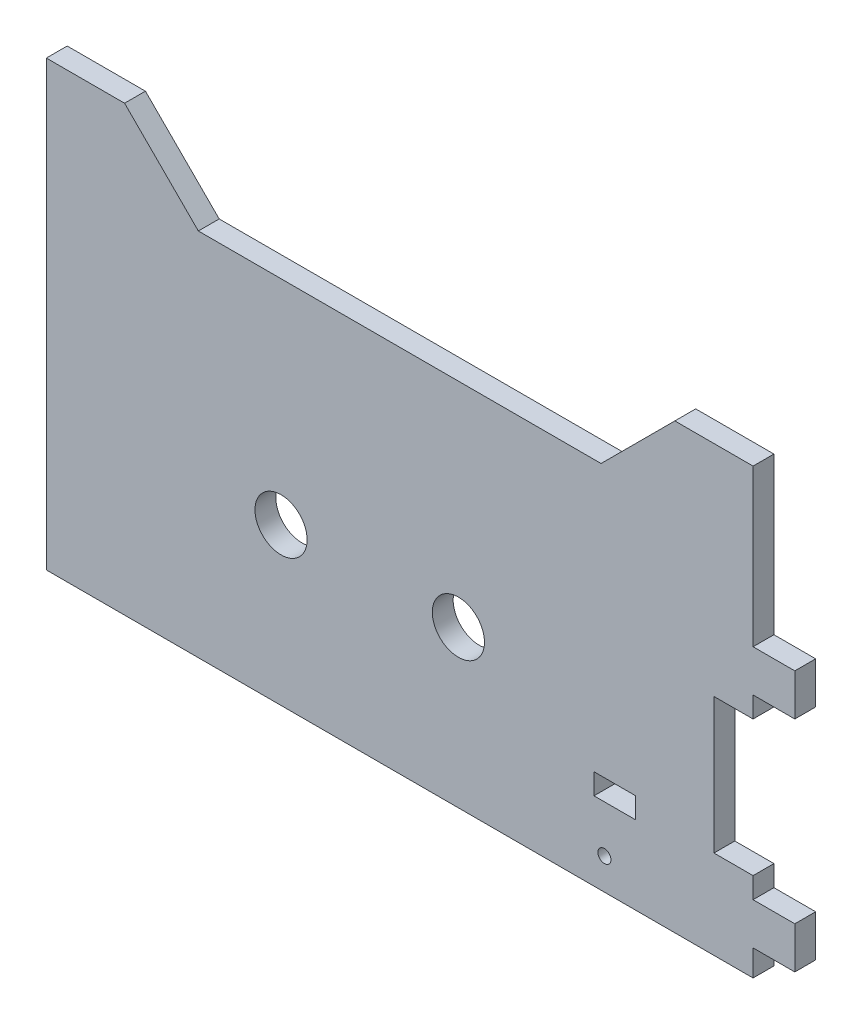
SolidWorks part; units mm, degrees
ref_plane "Front Plane" through (0, 0, 0) normal (0, 0, 1) x (1, 0, 0)
ref_plane "Top Plane" through (0, 0, 0) normal (0, 1, 0) x (1, 0, 0)
ref_plane "Right Plane" through (0, 0, 0) normal (1, 0, 0) x (0, 0, -1)
sketch "Sketch1" plane through (0, 0, 0) normal (0, 0, 1) x (1, 0, 0)
  line L0 (49, 30) -> (56.5, 30)
  line L1 (-79, -30) -> (49, -30)
  line L2 (-79, -30) -> (-79, 30)
  line L3 (-79, 30) -> (49, 30)
  line L6 (56.5, 13) -> (49, 13)
  line L7 (49, 13) -> (49, -13)
  line L8 (49, -13) -> (56.5, -13)
  line L10 (56.5, -30) -> (49, -30)
  line L11 (56.5, 30) -> (56.5, 13) construction
  line L12 (56.5, -13) -> (56.5, -30) construction
  line L13 (56.5, 30) -> (56.5, 25)
  line L14 (56.5, 25) -> (64.5, 25)
  line L15 (64.5, 25) -> (64.5, 17)
  line L16 (64.5, 17) -> (56.5, 17)
  line L17 (56.5, 17) -> (56.5, 13)
  line L18 (56.5, -13) -> (56.5, -17)
  line L19 (56.5, -17) -> (64.5, -17)
  line L20 (64.5, -17) -> (64.5, -25)
  line L21 (64.5, -25) -> (56.5, -25)
  line L22 (56.5, -25) -> (56.5, -30)
  line L23 (49, 30) -> (49, -30) construction
  line L24 (26, -11) -> (34, -11)
  line L25 (26, -11) -> (26, -15)
  line L26 (26, -15) -> (34, -15)
  line L27 (34, -11) -> (34, -15)
  circle A0 centre (0, 0) radius 5
  circle A3 centre (-34, 0) radius 5
  circle A4 centre (28, -24) radius 1.25
  point P1 (0, 0)
  dimension "D3" = 128
  dimension "D4" = 6
  dimension "D5" = 10
  dimension "D1" = 45
  dimension "D7" = 5
  dimension "D17" = 2.5
  dimension "D18" = 107
  dimension "D19" = 30
  dimension "D22" = 10
  dimension "D6" = 34
  dimension "D8" = 26
  dimension "D9" = 5
  dimension "D10" = 7.5
  dimension "D11" = 8
  dimension "D12" = 8
  dimension "D13" = 8
  dimension "D14" = 4
  dimension "D15" = 15
  dimension "D16" = 15
  dimension "D20" = 4
  dimension "D21" = 4
  dimension "D23" = 30
  dimension "D24" = 8
extrude "Boss-Extrude1" add sketch "Sketch1" along normal blind 4
sketch "Sketch2" plane through (0, 0, 0) normal (0, 0, 1) x (1, 0, 0)
  line L0 (-79, 30) -> (56.5, 30)
  line L1 (56.5, 30) -> (56.5, 55)
  line L2 (56.5, 55) -> (41.5, 55)
  line L3 (41.5, 55) -> (27.3579, 40.8579)
  line L4 (27.3579, 40.8579) -> (-49.8579, 40.8579)
  line L5 (-49.8579, 40.8579) -> (-64, 55)
  line L6 (-64, 55) -> (-79, 55)
  line L7 (-79, 55) -> (-79, 30)
  dimension "D1" = 25
  dimension "D2" = 15
  dimension "D3" = 20
  dimension "D4" = 135
extrude "Boss-Extrude2" add sketch "Sketch2" along normal blind 4
